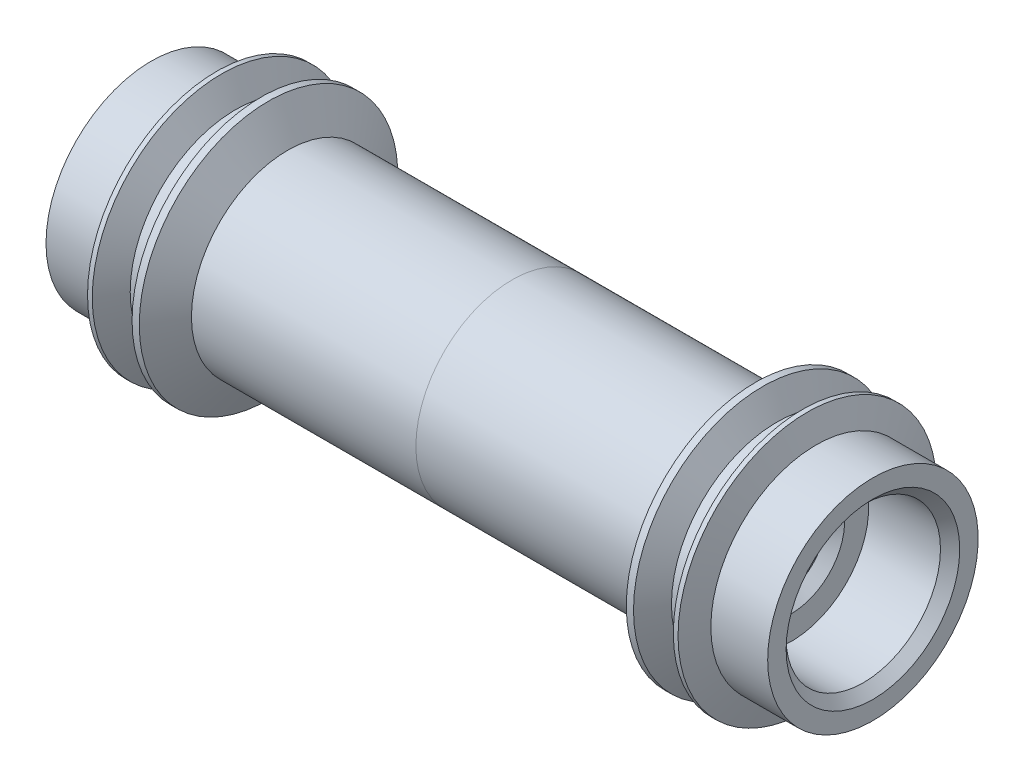
SolidWorks part; units mm, degrees
ref_plane "Front Plane" through (0, 0, 0) normal (0, 0, 1) x (1, 0, 0)
ref_plane "Top Plane" through (0, 0, 0) normal (0, 1, 0) x (1, 0, 0)
ref_plane "Right Plane" through (0, 0, 0) normal (1, 0, 0) x (0, 0, -1)
sketch "Sketch2" plane through (0, 0, 0) normal (0, 0, 1) x (1, 0, 0)
  line L0 (0, 0) -> (0, 28.4375) construction
  line L1 (-19.05, 4.075) -> (-14.75, 4.075) construction
  line L2 (-19.05, 4.075) -> (-19.05, -4.075) construction
  line L3 (-19.05, -4.075) -> (-14.75, -4.075) construction
  line L4 (-14.75, 4.075) -> (-14.75, -4.075) construction
  line L5 (-19.05, 4.075) -> (-14.75, -4.075) construction
  line L6 (-19.05, -4.075) -> (-14.75, 4.075) construction
  line L7 (14.75, 4.5) -> (48.8332, 4.5) construction
  line L8 (14.75, 4.5) -> (14.75, -4.5) construction
  line L9 (14.75, -4.5) -> (48.8332, -4.5) construction
  line L10 (48.8332, 4.5) -> (48.8332, -4.5) construction
  line L11 (14.75, 4.5) -> (48.8332, -4.5) construction
  line L12 (14.75, -4.5) -> (48.8332, 4.5) construction
  line L13 (-19.05, 0) -> (48.8332, 0) construction
  line L14 (-19.05, 5.5562) -> (-16.05, 5.5562)
  line L15 (-16.05, 5.5562) -> (-15.5878, 6.8262)
  line L16 (-15.5878, 6.8262) -> (-15.3382, 6.8262)
  line L19 (-13.2368, 6.8262) -> (-12.8558, 6.8262)
  line L20 (-12.8558, 6.8262) -> (-11.8476, 5.08)
  line L21 (-11.8476, 5.08) -> (0, 5.08)
  line L22 (-19.05, 5.5562) -> (-19.05, 4.075)
  line L23 (-19.05, 4.075) -> (-14.75, 4.075)
  line L24 (-14.75, 4.075) -> (-14.75, 0)
  line L25 (-14.75, 0) -> (0, 0)
  line L26 (0, 0) -> (0, 5.08)
  line L27 (-33.5594, -5.5562) -> (-33.5594, 5.5562) construction
  line L28 (-14.2875, 5.5562) -> (-14.2875, 7.68) construction
  line L29 (-14.2875, 5.5562) -> (14.2875, 5.5562) construction
  line L30 (-19.05, 5.5562) -> (19.05, 5.5562) construction
  line L31 (0, 1.625) -> (-6.5, 1.625)
  line L32 (-6.5, 1.625) -> (-8.125, 0)
  line L33 (-6.5, 1.625) -> (-6.5, -1.625) construction
  line L34 (-6.5, 1.625) -> (6.5, 1.625) construction
  line L35 (-14.75, 1.905) -> (-9.098, 1.905)
  line L36 (-9.098, 1.905) -> (-9.098, 0)
  line L37 (-14.75, 2.805) -> (-14.242, 2.297)
  line L38 (-9.098, 1.905) -> (-22.098, 1.905) construction
  line L39 (-9.098, 1.905) -> (-9.098, -1.905) construction
  line L40 (-9.098, -1.905) -> (-22.098, -1.905) construction
  line L41 (-22.098, 1.905) -> (-22.098, -1.905) construction
  line L42 (-14.242, 2.297) -> (-14.242, 0)
  line L43 (-15.3382, 6.8262) -> (-14.605, 5.5562)
  line L44 (-14.605, 5.5562) -> (-13.97, 5.5562)
  line L45 (-13.97, 5.5562) -> (-13.2368, 6.8262)
  point P0 (-16.9, 0)
  point P5 (31.7916, 0)
  point P27 (-33.5594, 0)
  point P28 (-13.0463, 6.8262)
  point P29 (-6.5, 0)
  point P33 (0, 5.5562)
  point P36 (0, 1.625)
  point P48 (-9.098, 0)
  point P51 (0, 5.5562)
  point P54 (-14.2875, 5.5562)
  dimension "D1" = 4.3
  dimension "D3" = 5.08
  dimension "D4" = 11.1125
  dimension "D5" = 8.15
  dimension "D6" = 60
  dimension "D8" = 1.27
  dimension "D9" = 70
  dimension "D10" = 28.575
  dimension "D12" = 0.381
  dimension "D13" = 45
  dimension "D14" = 13
  dimension "D15" = 3.25
  dimension "D16" = 3.81
  dimension "D17" = 3.048
  dimension "D18" = 1.27
  dimension "D19" = 0.508
  dimension "D20" = 45
  dimension "D21" = 13
  dimension "D11" = 38.1
  dimension "D22" = 3
  dimension "D7" = 60
  dimension "D23" = 0.635
revolve "Revolve1" add sketch "Sketch2" angle 360 about L13 region at (-8.6285, 3.5856, 0)
chamfer "Chamfer1" distance 0.508 angle 45 1 edges at (-19.05, 0, 4.075)
mirror "Mirror1" about plane through (0, 0, 0) normal (1, 0, 0) of bodies 101
equation "\"D15@Sketch2\"=3mm+.25mm"
equation "\"D1@Sketch2\"=4.3mm"
